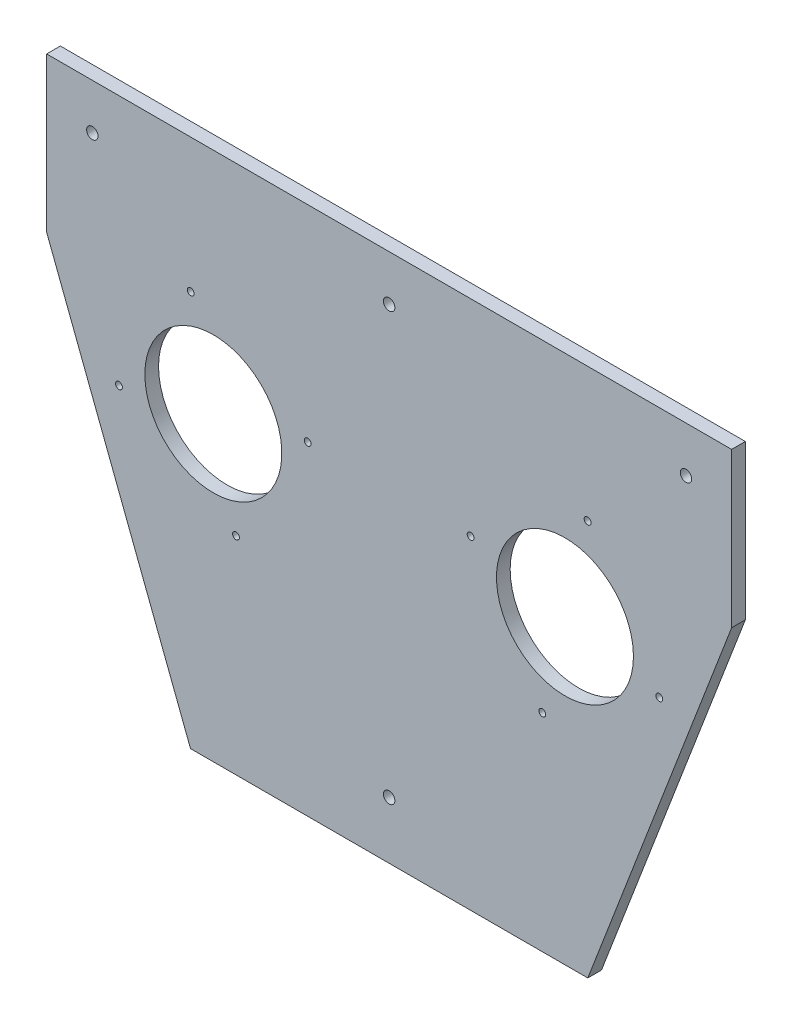
SolidWorks part; units mm, degrees
ref_plane "Front Plane" through (0, 0, 0) normal (0, 0, 1) x (1, 0, 0)
ref_plane "Top Plane" through (0, 0, 0) normal (0, 1, 0) x (1, 0, 0)
ref_plane "Right Plane" through (0, 0, 0) normal (1, 0, 0) x (0, 0, -1)
sketch "Sketch1" plane through (0, 0, 0) normal (0, 0, 1) x (1, 0, 0)
  line L0 (-130, 93.5) -> (130, 93.5) construction
  line L1 (-150, 45.8381) -> (-87, -118.5)
  line L2 (-87, -118.5) -> (87, -118.5)
  line L3 (87, -118.5) -> (150, 45.8381)
  line L4 (0, -93.5) -> (0, -118.5) construction
  line L6 (0, -93.5) -> (0, 93.5) construction
  line L7 (-150, 113.5) -> (150, 113.5)
  line L8 (150, 113.5) -> (150, 45.8381)
  line L11 (-150, 45.8381) -> (-150, 113.5)
  circle A4 centre (0, -93.5) radius 2.5
  circle A20 centre (0, 93.5) radius 2.5
  circle A21 centre (-130, 93.5) radius 2.5
  circle A22 centre (130, 93.5) radius 2.5
  point P12 (0, 93.5)
  point P45 (0, 113.5)
  dimension "D2" = 5
  dimension "D9" = 260
  dimension "D3" = 20
  dimension "D6" = 20
  dimension "D1" = 25
  dimension "D4" = 174
  dimension "D5" = 176
  dimension "D7" = 187
extrude "Boss-Extrude1" add sketch "Sketch1" along normal blind 6
sketch "Sketch2" plane through (0, 0, 6) normal (0, 0, 1) x (1, 0, 0)
  line L0 (118.326, 3.5796) -> (35.674, 23.4204) construction
  line L1 (67.0796, -27.826) -> (86.9204, 54.826) construction
  line L2 (0, 0) -> (0, 93.5) construction
  line L3 (150, 113.5) -> (-150, 113.5) construction
  circle A0 centre (77, 13.5) radius 42.5 construction
  circle A1 centre (35.674, 23.4204) radius 1.5
  circle A2 centre (86.9204, 54.826) radius 1.5
  circle A3 centre (118.326, 3.5796) radius 1.5
  circle A4 centre (67.0796, -27.826) radius 1.5
  circle A5 centre (77, 13.5) radius 30
  circle A6 centre (-35.674, 23.4204) radius 1.5
  circle A7 centre (-86.9204, 54.826) radius 1.5
  circle A8 centre (-67.0796, -27.826) radius 1.5
  circle A9 centre (-118.326, 3.5796) radius 1.5
  circle A10 centre (-77, 13.5) radius 42.5 construction
  circle A11 centre (-77, 13.5) radius 30
  point P6 (77, 13.5)
  point P27 (-77, 13.5)
  dimension "D1" = 85
  dimension "D2" = 3
  dimension "D3" = 60
  dimension "D4" = 100
  dimension "D5" = 77
extrude "Cut-Extrude1" cut sketch "Sketch2" against normal blind 10
equation "\"carbon_fiber_tube_diam\"= 1in, 25.4mm"
equation "\"clip_tube_diam\"= 6mm"
equation "\"middle_tube_len\"= 500mm"
equation "\"horizontal_pipe_spacing\"= 260mm"
equation "\"D9@Sketch1\"=\"horizontal_pipe_spacing\""
equation "\"belly_plate_width\" = 176mm"
equation "\"belly_bottom_width\" = 174mm"
equation "\"belly_length\"  = 500mm"
